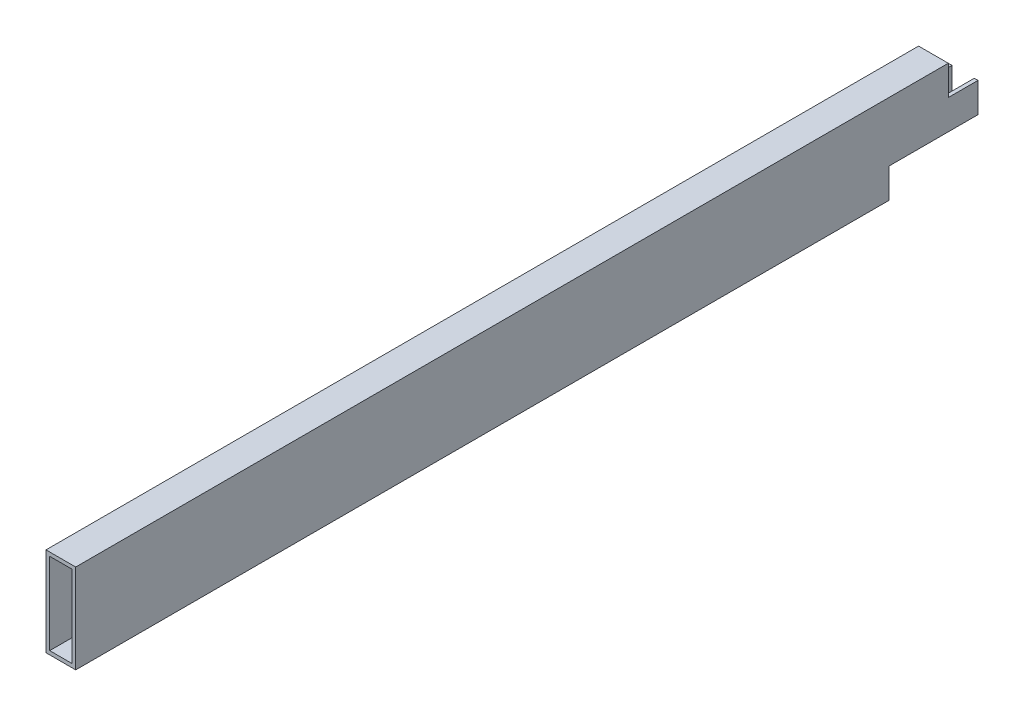
SolidWorks part; units mm, degrees
ref_plane "Front Plane" through (0, 0, 0) normal (0, 0, 1) x (1, 0, 0)
ref_plane "Top Plane" through (0, 0, 0) normal (0, 1, 0) x (1, 0, 0)
ref_plane "Right Plane" through (0, 0, 0) normal (1, 0, 0) x (0, 0, -1)
sketch "Sketch1" plane through (0, 0, 0) normal (0, 0, 1) x (1, 0, 0)
  line L1 (-12.7, -38.1) -> (12.7, -38.1)
  line L2 (-12.7, -38.1) -> (-12.7, 38.1)
  line L3 (-12.7, 38.1) -> (12.7, 38.1)
  line L4 (12.7, -38.1) -> (12.7, 38.1)
  line L5 (-12.7, -38.1) -> (12.7, 38.1) construction
  line L6 (-12.7, 38.1) -> (12.7, -38.1) construction
  point P0 (0, 0)
  dimension "D1" = 25.4
  dimension "D2" = 76.2
extrude "Boss-Extrude1" add sketch "Sketch1" along normal mid plane 771.398
shell "Shell1" thickness 3.175 removed face at (0, 0, -385.699) removed face at (0, 0, 385.699)
sketch "Sketch2" plane through (12.7, 0, 0) normal (1, 0, 0) x (0, 0, -1)
  line L1 (385.699, -38.1) -> (309.499, -38.1)
  line L2 (385.699, -38.1) -> (385.699, -12.7)
  line L3 (385.699, -12.7) -> (309.499, -12.7)
  line L4 (309.499, -38.1) -> (309.499, -12.7)
  dimension "D1" = 25.4
  dimension "D2" = 76.2
extrude "Cut-Extrude1" cut sketch "Sketch2" against normal through all
sketch "Sketch3" plane through (12.7, 0, 0) normal (1, 0, 0) x (0, 0, -1)
  line L1 (385.699, 38.1) -> (360.299, 38.1)
  line L2 (385.699, 38.1) -> (385.699, 12.7)
  line L3 (385.699, 12.7) -> (360.299, 12.7)
  line L4 (360.299, 38.1) -> (360.299, 12.7)
  dimension "D1" = 25.4
extrude "Cut-Extrude2" cut sketch "Sketch3" against normal through all
